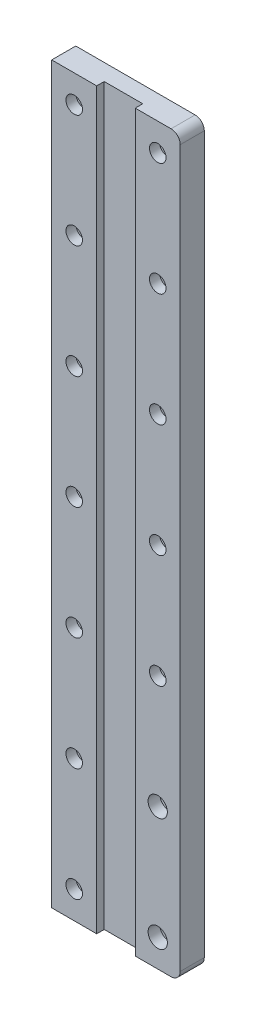
SolidWorks part; units mm, degrees
ref_plane "Front Plane" through (0, 0, 0) normal (0, 0, 1) x (1, 0, 0)
ref_plane "Top Plane" through (0, 0, 0) normal (0, 1, 0) x (1, 0, 0)
ref_plane "Right Plane" through (0, 0, 0) normal (1, 0, 0) x (0, 0, -1)
sketch "Sketch1" plane through (0, 0, 0) normal (0, 0, 1) x (1, 0, 0)
  line L1 (35, 200) -> (-35, 200)
  line L2 (35, 200) -> (35, -200)
  line L3 (35, -200) -> (-35, -200)
  line L4 (-35, 200) -> (-35, -200)
  line L5 (35, 200) -> (-35, -200) construction
  line L6 (35, -200) -> (-35, 200) construction
  point P0 (0, 0)
  dimension "D1" = 400
  dimension "D2" = 70
extrude "Boss-Extrude1" add sketch "Sketch1" along normal blind 9
sketch "Sketch3" plane through (0, 0, 9) normal (0, 0, 1) x (1, 0, 0)
  line L0 (-35, -200) -> (35, -200) construction
  line L1 (35, 200) -> (10.5, 200)
  line L2 (35, 200) -> (35, -200)
  line L3 (35, -200) -> (10.5, -200)
  line L4 (10.5, 200) -> (10.5, -200)
  line L5 (35, 200) -> (-35, 200) construction
  line L6 (-35, -200) -> (-10.5, -200)
  line L7 (-35, -200) -> (-35, 200)
  line L8 (-35, 200) -> (-10.5, 200)
  line L9 (-10.5, -200) -> (-10.5, 200)
  dimension "D1" = 21
extrude "Boss-Extrude2" add sketch "Sketch3" along normal blind 13.1 from surface starting at face at (0, 0, 0)
fillet "Fillet1" radius 5 2 edges at (35, -200, 6.55) (35, 200, 6.55)
sketch "Sketch4" plane through (0, 0, 13.1) normal (0, 0, 1) x (1, 0, 0)
  line L0 (-22.75, 200) -> (-22.75, 185) construction
  line L3 (-35, 200) -> (-10.5, 200) construction
  line L4 (-22.75, 185) -> (-22.75, 123.3333) construction
  line L5 (-22.75, 123.3333) -> (-22.75, 61.6667) construction
  line L6 (-22.75, 61.6667) -> (-22.75, 0) construction
  line L7 (-22.75, 0) -> (-22.75, -61.6667) construction
  line L8 (-22.75, -61.6667) -> (-22.75, -123.3333) construction
  line L9 (-22.75, -123.3333) -> (-22.75, -185) construction
  line L10 (-22.75, -185) -> (-22.75, -200) construction
  line L11 (-10.5, -200) -> (-35, -200) construction
  line L12 (0, 200) -> (0, -200) construction
  line L13 (10.5, 200) -> (-10.5, 200) construction
  line L14 (-10.5, -200) -> (10.5, -200) construction
  circle A0 centre (-22.75, 185) radius 2.75
  circle A1 centre (-22.75, 123.3333) radius 2.75
  circle A2 centre (-22.75, 61.6667) radius 2.75
  circle A3 centre (-22.75, 0) radius 2.75
  circle A4 centre (-22.75, -61.6667) radius 2.75
  circle A5 centre (-22.75, -123.3333) radius 2.75
  circle A6 centre (-22.75, -185) radius 2.75
  circle A7 centre (22.75, -185) radius 2.75
  circle A8 centre (22.75, -123.3333) radius 2.75
  circle A9 centre (22.75, -61.6667) radius 2.75
  circle A10 centre (22.75, 0) radius 2.75
  circle A11 centre (22.75, 61.6667) radius 2.75
  circle A12 centre (22.75, 123.3333) radius 2.75
  circle A13 centre (22.75, 185) radius 2.75
  dimension "D2" = 5.5
  dimension "D1" = 15
extrude "Cut-Extrude1" cut sketch "Sketch4" against normal through all
sketch "Sketch5" plane through (0, 0, 13.1) normal (0, 0, 1) x (1, 0, 0)
  circle A0 centre (-22.75, 185) radius 4.5
  circle A1 centre (22.75, 185) radius 4.5
  circle A2 centre (22.75, 123.3333) radius 4.5
  circle A3 centre (-22.75, 123.3333) radius 4.5
  circle A4 centre (-22.75, 61.6667) radius 4.5
  circle A5 centre (22.75, 61.6667) radius 4.5
  circle A6 centre (22.75, 0) radius 4.5
  circle A7 centre (-22.75, 0) radius 4.5
  circle A8 centre (-22.75, -61.6667) radius 4.5
  circle A9 centre (22.75, -61.6667) radius 4.5
  circle A10 centre (22.75, -123.3333) radius 4.5
  circle A11 centre (-22.75, -123.3333) radius 4.5
  circle A12 centre (-22.75, -185) radius 4.5
  circle A13 centre (22.75, -185) radius 4.5
  dimension "D1" = 9
extrude "Cut-Extrude2" cut sketch "Sketch5" against normal blind 5.5
sketch "Sketch6" plane through (0, 0, 13.1) normal (0, 0, 1) x (1, 0, 0)
  circle A0 centre (22.75, -123.3333) radius 3.3
  circle A1 centre (22.75, -185) radius 3.3
  dimension "D1" = 6.6
extrude "Cut-Extrude3" cut sketch "Sketch6" against normal through all
sketch "Sketch7" plane through (0, 0, 13.1) normal (0, 0, 1) x (1, 0, 0)
  circle A0 centre (22.75, -123.3333) radius 5.25
  circle A1 centre (22.75, -185) radius 5.25
  dimension "D1" = 10.5
extrude "Cut-Extrude4" cut sketch "Sketch7" against normal blind 6.4
sketch "Sketch8" [suppressed] plane through (0, 0, 13.1) normal (0, 0, 1) x (1, 0, 0)
  circle A0 centre (22.75, 185) radius 3.3
  circle A1 centre (22.75, 123.3333) radius 3.3
  dimension "D1" = 6.6
extrude "Cut-Extrude5" [suppressed] cut sketch "Sketch8" against normal through all
sketch "Sketch9" [suppressed] plane through (0, 0, 13.1) normal (0, 0, 1) x (1, 0, 0)
  circle A0 centre (22.75, 185) radius 5.25
  circle A1 centre (22.75, 123.3333) radius 5.25
  dimension "D1" = 10.5
extrude "Cut-Extrude6" [suppressed] cut sketch "Sketch9" against normal blind 6.4
equation "\"M5_Thread\"= 4.2mm"
equation "\"M5_Pass\"= 5.5"
equation "\"M6_Thread\"= 5mm"
equation "\"M6_Pass\"= 6.6"
equation "\"M5_Head\"= 9mm"
equation "\"M6_Head\"= 10.5"
equation "\"M5_HeadDepth\"= 5.5"
equation "\"M6_HeadDepth\"= 5.9 + .5"
equation "\"D2@Sketch4\"=\"M5_Pass\""
equation "\"D1@Sketch5\"=\"M5_Head\""
equation "\"D1@Cut-Extrude2\"=\"M5_HeadDepth\""
equation "\"D1@Sketch6\"=\"M6_Pass\""
equation "\"D1@Sketch7\"=\"M6_Head\""
equation "\"D1@Cut-Extrude4\"=\"M6_HeadDepth\""
equation "\"D1@Cut-Extrude6\"=\"M6_HeadDepth\""
